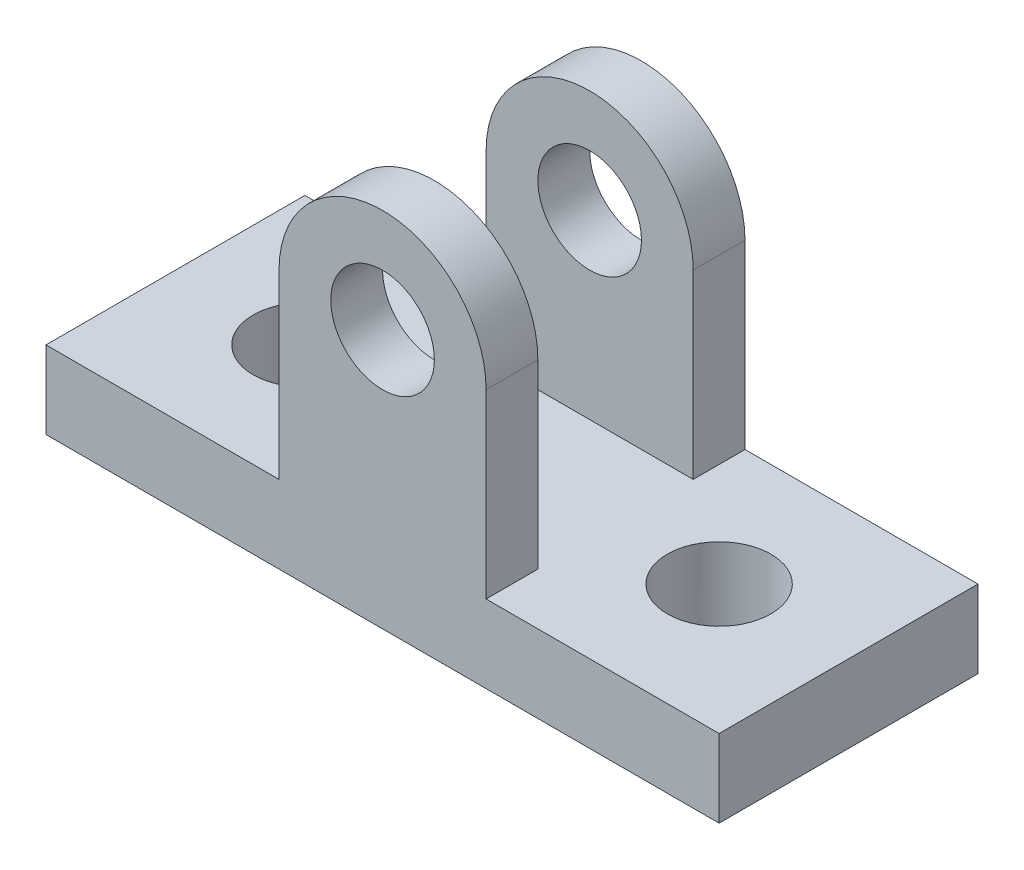
SolidWorks part; units mm, degrees
ref_plane "Front Plane" through (0, 0, 0) normal (0, 0, 1) x (1, 0, 0)
ref_plane "Top Plane" through (0, 0, 0) normal (0, 1, 0) x (1, 0, 0)
ref_plane "Right Plane" through (0, 0, 0) normal (1, 0, 0) x (0, 0, -1)
sketch "Sketch1" plane through (0, 0, 0) normal (0, 0, 1) x (1, 0, 0)
  line L0 (-65, 0) -> (-65, 15)
  line L1 (-65, 15) -> (-20, 15)
  line L2 (-20, 15) -> (-20, 50)
  line L4 (20, 50) -> (20, 15)
  line L5 (20, 15) -> (65, 15)
  line L6 (65, 15) -> (65, 0)
  line L7 (65, 0) -> (-65, 0)
  arc A0 (20, 50) -> (-20, 50) centre (0, 50) ccw
  point P11 (0, 0)
  dimension "D6" = 40
  dimension "D1" = 130
  dimension "D2" = 65
  dimension "D3" = 40
  dimension "D4" = 20
  dimension "D5" = 15
  dimension "D7" = 35
extrude "Boss-Extrude1" add sketch "Sketch1" along normal blind 50
sketch "Sketch2" plane through (0, 15, 0) normal (0, 1, 0) x (1, 0, 0)
  line L2 (-20, -50) -> (-65, -50) construction
  line L3 (65, -50) -> (20, -50) construction
  circle A0 centre (-40, -25) radius 10
  circle A1 centre (40, -25) radius 10
  point P7 (-67.0119, 22.4831)
  point P8 (0, 0)
  point P9 (0, 0)
  point P12 (33.4419, -25.0641)
  point P15 (38.439, -37.3645)
  dimension "D4" = 20
  dimension "D1" = 80
  dimension "D2" = 40
  dimension "D3" = 25
  dimension "D5" = 25
extrude "Cut-Extrude1" cut sketch "Sketch2" against normal blind 25 contours A0
extrude "Cut-Extrude2" cut sketch "Sketch2<3>" against normal blind 25 contours A1
sketch "Sketch2<3>" plane through (0, 15, 0) normal (0, 1, 0) x (1, 0, 0) same geometry as "Sketch2"
sketch "Sketch3" plane through (0, 15, 0) normal (0, 1, 0) x (1, 0, 0)
  line L0 (-20, -50) -> (-20, 0) construction
  line L1 (-20, -10) -> (20, -10)
  line L2 (-20, -10) -> (-20, -40)
  line L3 (-20, -40) -> (20, -40)
  line L4 (20, -10) -> (20, -40)
  line L5 (20, -50) -> (20, 0) construction
  line L6 (20, 0) -> (-20, 0) construction
  line L7 (-20, -50) -> (20, -50) construction
  dimension "D1" = 10
  dimension "D2" = 10
extrude "Cut-Extrude3" cut sketch "Sketch3" along normal through all
sketch "Sketch4" plane through (0, 0, 50) normal (0, 0, 1) x (1, 0, 0)
  line L0 (-20, 15) -> (-65, 15) construction
  circle A0 centre (0, 50) radius 10
  dimension "D1" = 20
  dimension "D2" = 35
extrude "Cut-Extrude4" cut sketch "Sketch4" against normal through all contours A0
